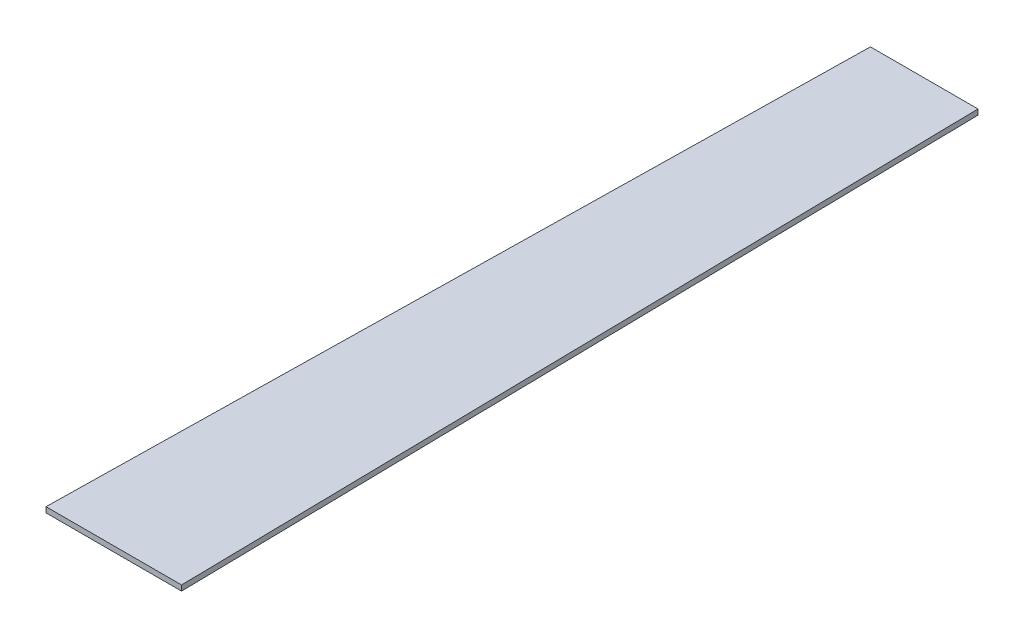
SolidWorks part; units mm, degrees
ref_plane "Front Plane" through (0, 0, 0) normal (0, 0, 1) x (1, 0, 0)
ref_plane "Top Plane" through (0, 0, 0) normal (0, 1, 0) x (1, 0, 0)
ref_plane "Right Plane" through (0, 0, 0) normal (1, 0, 0) x (0, 0, -1)
sketch "Sketch1" plane through (0, 0, 0) normal (0, 1, 0) x (1, 0, 0)
  line L4 (0, 0) -> (2000, 0)
  line L5 (2000, 0) -> (2260, -15067.757)
  line L6 (2260, -15067.757) -> (-260, -15067.757)
  line L7 (0, 0) -> (-260, -15067.757)
  point P3 (1000, 0)
  point P7 (1000, -15067.757)
  dimension "D1" = 2000
  dimension "D2" = 2520
  dimension "D3" = 15070
  dimension "D4" = 15070
extrude "Boss-Extrude1" add sketch "Sketch1" along normal blind 100
